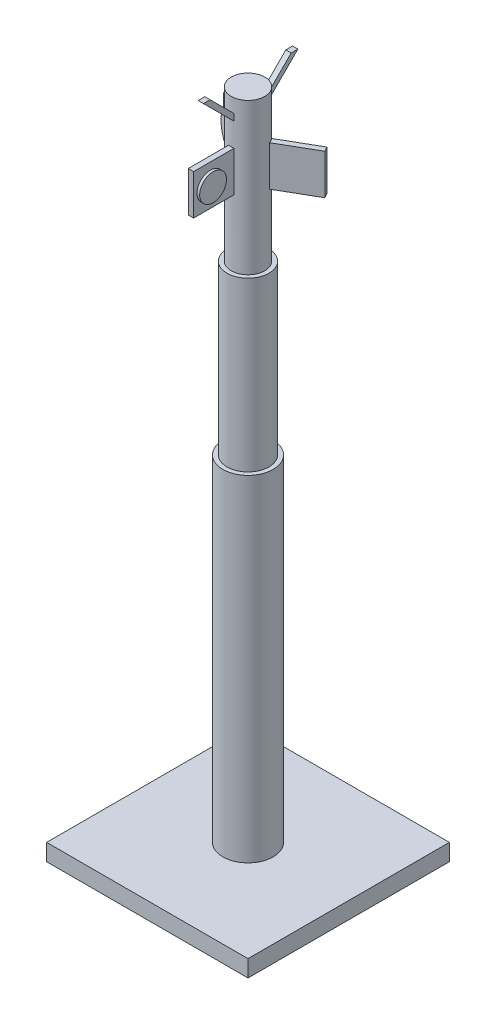
SolidWorks part; units mm, degrees
ref_plane "Front Plane" through (0, 0, 0) normal (0, 0, 1) x (1, 0, 0)
ref_plane "Top Plane" through (0, 0, 0) normal (0, 1, 0) x (1, 0, 0)
ref_plane "Right Plane" through (0, 0, 0) normal (1, 0, 0) x (0, 0, -1)
sketch "Sketch1" plane through (0, 0, 0) normal (0, 1, 0) x (1, 0, 0)
  circle A0 centre (0, 0) radius 7.5
  dimension "D1" = 15
extrude "Boss-Extrude1" add sketch "Sketch1" along normal blind 100
sketch "Sketch2" plane through (0, 100, 0) normal (0, 1, 0) x (1, 0, 0)
  circle A0 centre (0, 0) radius 6.25
  dimension "D1" = 12.5
extrude "Boss-Extrude2" add sketch "Sketch2" along normal blind 50
sketch "Sketch3" plane through (0, 0, 0) normal (0, -1, 0) x (1, 0, 0)
  line L1 (-30, 30) -> (30, 30)
  line L2 (-30, 30) -> (-30, -30)
  line L3 (-30, -30) -> (30, -30)
  line L4 (30, 30) -> (30, -30)
  line L5 (-30, 30) -> (30, -30) construction
  line L6 (-30, -30) -> (30, 30) construction
  point P0 (0, 0)
  dimension "D1" = 60
  dimension "D2" = 60
extrude "Boss-Extrude3" add sketch "Sketch3" along normal blind 5
sketch "Sketch4" plane through (0, 150, 0) normal (0, 1, 0) x (1, 0, 0)
  circle A0 centre (0, 0) radius 5
  dimension "D1" = 10
extrude "Boss-Extrude4" add sketch "Sketch4" along normal blind 45
sketch "Sketch5" plane through (0, 0, 0) normal (1, 0, 0) x (0, 0, -1)
  line L0 (-5, 182) -> (-17, 182)
  line L1 (-5, 195) -> (-5, 150) construction
  line L2 (-17, 182) -> (-17, 170)
  line L3 (-17, 170) -> (-5, 170)
  line L6 (0, 195) -> (0, 183.4322) construction
  line L10 (5, 195) -> (-5, 195) construction
  line L11 (-5, 182) -> (-2.5, 182)
  line L13 (-2.5, 170) -> (-5, 170)
  line L14 (-2.5, 182) -> (-2.5, 170)
  dimension "D1" = 12
  dimension "D2" = 12
  dimension "D3" = 13
extrude "Boss-Extrude5" add sketch "Sketch5" along normal blind 0.8 and the other way blind 0.8
sketch "Sketch6" plane through (0.8, 0, 0) normal (1, 0, 0) x (0, 0, -1)
  line L2 (-17, 182) -> (-17, 170) construction
  circle A0 centre (-12, 175.8747) radius 4
  dimension "D2" = 8
  dimension "D1" = 5
extrude "Boss-Extrude6" add sketch "Sketch6" along normal blind 0.8
pattern_circular "CirPattern2" count 3 over 360 about axis through (0, 195, 0) along (0, 1, 0) of "Boss-Extrude5", "Boss-Extrude6"
sketch "Sketch7" plane through (0, 0, 0) normal (1, 0, 0) x (0, 0, -1)
  line L1 (-5, 191) -> (-0.6225, 186.6225)
  line L5 (0, 195) -> (0, 191.2817) construction
  line L6 (-0.6225, 186.6225) -> (-1.6225, 185.6225)
  line L20 (5, 195) -> (-5, 195) construction
  line L25 (-5, 191) -> (-12.0711, 198.0711)
  line L26 (-5, 195) -> (-5, 182) construction
  line L27 (-12.0711, 198.0711) -> (-14.0711, 198.0711)
  line L28 (-14.0711, 198.0711) -> (-5, 189)
  line L29 (-5, 189) -> (-1.6225, 185.6225)
  line L30 (5, 191) -> (0.6225, 186.6225)
  line L31 (5, 191) -> (12.0711, 198.0711)
  line L32 (12.0711, 198.0711) -> (14.0711, 198.0711)
  line L33 (14.0711, 198.0711) -> (5, 189)
  line L34 (5, 189) -> (1.6225, 185.6225)
  line L35 (0.6225, 186.6225) -> (1.6225, 185.6225)
  dimension "D1" = 2
  dimension "D2" = 10
  dimension "D3" = 45
  dimension "D4" = 4
extrude "Boss-Extrude7" add sketch "Sketch7" along normal blind 0.8 and the other way blind 0.8 separate body contours L31 L32 L33 L34 L35 L30 | L6 L29 L28 L27 L25 L1
